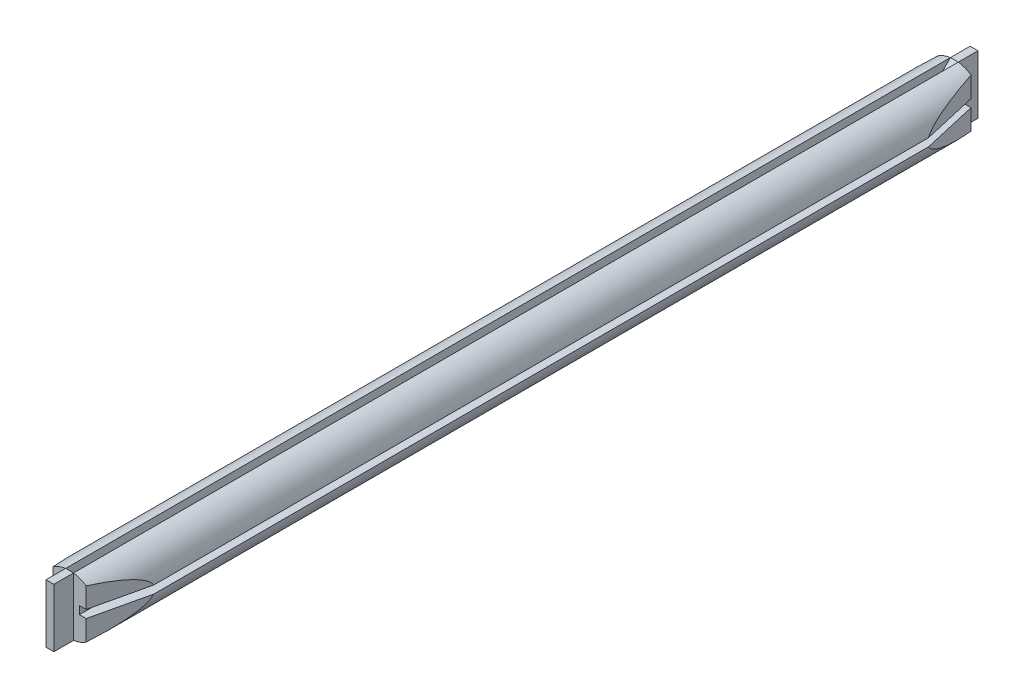
SolidWorks part; units mm, degrees
ref_plane "Front Plane" through (0, 0, 0) normal (0, 0, 1) x (1, 0, 0)
ref_plane "Top Plane" through (0, 0, 0) normal (0, 1, 0) x (1, 0, 0)
ref_plane "Right Plane" through (0, 0, 0) normal (1, 0, 0) x (0, 0, -1)
sketch "Sketch1" plane through (0, 0, 0) normal (0, 0, 1) x (1, 0, 0)
  line L0 (3.3454, 176.2824) -> (3.3454, 56.4598) construction
  line L1 (-6.6546, 55.7901) -> (-6.6546, 6.4598)
  line L2 (-6.6546, 6.4598) -> (13.3454, 6.4598)
  line L3 (13.3454, 55.7901) -> (13.3454, 6.4598)
  line L4 (-25.8595, -18.5402) -> (28.5608, -18.5402) construction
  line L5 (77.6757, -28.5402) -> (28.3454, -28.5402)
  line L6 (77.6757, -8.5402) -> (28.3454, -8.5402)
  line L7 (28.3454, -8.5402) -> (28.3454, -28.5402)
  line L8 (-6.6546, -92.8705) -> (-6.6546, -43.5402)
  line L9 (13.3454, -92.8705) -> (13.3454, -43.5402)
  line L10 (13.3454, -43.5402) -> (-6.6546, -43.5402)
  line L11 (-70.985, -8.5402) -> (-21.6546, -8.5402)
  line L12 (-70.985, -28.5402) -> (-21.6546, -28.5402)
  line L13 (-21.6546, -28.5402) -> (-21.6546, -8.5402)
  line L14 (3.3454, 56.4598) -> (3.3454, 6.4598) construction
  line L15 (3.3454, 6.4598) -> (3.3454, -262.3603) construction
  arc A1 (-6.6546, 55.7901) -> (-70.985, -8.5402) centre (3.3454, -18.5402) ccw
  arc A2 (-70.985, -28.5402) -> (-6.6546, -92.8705) centre (3.3454, -18.5402) ccw
  arc A3 (13.3454, -92.8705) -> (77.6757, -28.5402) centre (3.3454, -18.5402) ccw
  arc A4 (77.6757, -8.5402) -> (13.3454, 55.7901) centre (3.3454, -18.5402) ccw
  arc A5 (13.3454, 55.7901) -> (32.6342, 50.5044) centre (3.3454, -18.5402) cw
  point P1 (3.3454, 6.4598)
  point P4 (3.3454, 75.2096)
  point P23 (-96.6546, -18.5402)
  point P28 (3.3454, -18.5402)
  point P29 (3.3454, -18.5402)
  dimension "D1" = 20
  dimension "D2" = 150
  dimension "D3" = 50
extrude "Boss-Extrude1" add sketch "Sketch1" along normal blind 1125 contours L6 A4 L3 L2 L1 A1 L11 L13 L12 A2 L8 L10 L9 A3 L5 L7 region at (3.3454, -18.5402, 0)
sketch "Sketch2" plane through (0, 0, 0) normal (0, 1, 0) x (1, 0, 0)
  line L3 (-70.985, -1125) -> (-70.985, 0) construction
  line L4 (-70.985, -140) -> (-38.8198, 0)
  line L5 (-6.6546, 0) -> (-70.985, 0) construction
  line L7 (-70.985, -140) -> (-70.985, 0)
  line L9 (-70.985, 0) -> (-38.8198, 0)
  line L10 (3.3454, 0) -> (3.3454, -140) construction
  line L12 (77.6757, 0) -> (45.5105, 0)
  line L13 (77.6757, -140) -> (77.6757, 0)
  line L14 (77.6757, -140) -> (45.5105, 0)
extrude "Cut-Extrude1" cut sketch "Sketch2" against normal mid plane 220
sketch "Sketch3" plane through (-6.6546, 0, 0) normal (1, 0, 0) x (0, 0, -1)
  line L0 (0, 55.7901) -> (0, -92.8705)
  line L1 (0, -92.8705) -> (-74.3303, -18.5402)
  line L2 (-74.3303, -18.5402) -> (0, 55.7901)
extrude "Boss-Extrude2" add sketch "Sketch3" along normal up to surface (20 mm away) up to face at (13.3454, 31.125, 562.5)
sketch "Sketch4" plane through (0, 0, 0) normal (0, 0, -1) x (-1, 0, 0)
  line L0 (-28.3454, -18.5402) -> (21.6546, -18.5402)
  line L1 (-28.3454, -8.5402) -> (-28.3454, -28.5402) construction
  line L2 (21.6546, -28.5402) -> (21.6546, -8.5402) construction
  line L4 (-13.3454, 55.7901) -> (6.6546, 55.7901)
  line L5 (-13.3454, 55.7901) -> (-13.3454, -92.8705)
  line L6 (-13.3454, -92.8705) -> (6.6546, -92.8705)
  line L7 (6.6546, 55.7901) -> (6.6546, -92.8705)
  line L8 (-13.3454, 55.7901) -> (6.6546, -92.8705) construction
  line L9 (-13.3454, -92.8705) -> (6.6546, 55.7901) construction
  arc A0 (6.6546, -92.8705) -> (38.8198, -80.5652) centre (-3.3454, -18.5402) ccw construction
  point P6 (-3.3454, -18.5402)
  line M2 (-13.3454, -92.8705) -> (6.6546, -92.8705)
  line M10 (6.6546, 55.7901) -> (-13.3454, 55.7901)
extrude "Boss-Extrude3" add sketch "Sketch4" along normal blind 50 contours L7 L0 L5 M2 | L7 L5 L0 M10 region at (3.3454, 18.625, 0) region at (3.3454, -55.7054, 0)
ref_plane "Plane1" through (3.3454, 0, 0) normal (-1, 0, 0) x (0, 0, 1)
mirror "Mirror1" about plane through (0, 0, 1125) normal (0, 0, 1) of "Boss-Extrude1", "Cut-Extrude1", "Boss-Extrude2", "Boss-Extrude3"
